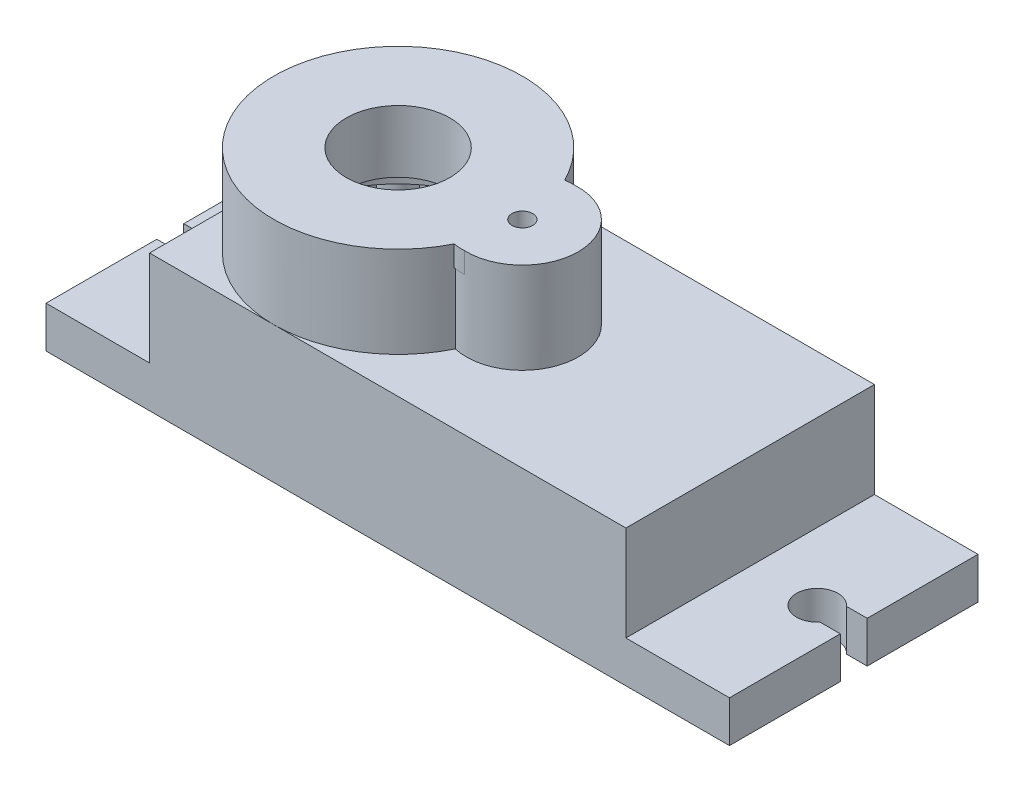
SolidWorks part; units mm, degrees
ref_plane "Front Plane" through (0, 0, 0) normal (0, 0, 1) x (1, 0, 0)
ref_plane "Top Plane" through (0, 0, 0) normal (0, 1, 0) x (1, 0, 0)
ref_plane "Right Plane" through (0, 0, 0) normal (1, 0, 0) x (0, 0, -1)
sketch "Sketch1" plane through (0, 0, 0) normal (0, 1, 0) x (1, 0, 0)
  line L1 (-11.5, -6) -> (11.5, -6)
  line L2 (-11.5, -6) -> (-11.5, 6)
  line L3 (-11.5, 6) -> (11.5, 6)
  line L4 (11.5, -6) -> (11.5, 6)
  line L5 (-11.5, -6) -> (11.5, 6) construction
  line L6 (-11.5, 6) -> (11.5, -6) construction
  point P0 (0, 0)
  dimension "D1" = 12
  dimension "D2" = 23
extrude "Boss-Extrude1" add sketch "Sketch1" along normal blind 6.6
sketch "Sketch2" plane through (11.5, 0, 0) normal (1, 0, 0) x (0, 0, -1)
  line L0 (-6, 0) -> (6, 0)
  line L1 (-6, 0) -> (-6, 2)
  line L2 (6, 0) -> (6, 2)
  line L3 (-6, 2) -> (6, 2)
  dimension "D1" = 2
extrude "Boss-Extrude2" add sketch "Sketch2" along normal blind 5 and the other way blind 28
sketch "Sketch3" plane through (0, 2, 0) normal (0, 1, 0) x (1, 0, 0)
  line L0 (16.5, 6) -> (16.5, -6) construction
  line L1 (16.5, 0.65) -> (15.5, 0.65)
  line L3 (16.5, -0.65) -> (15.5196, -0.65)
  line L5 (-16.5, 6) -> (-16.5, -6) construction
  line L7 (16.5, -0.65) -> (16.5, 0.65)
  line L9 (-16.5, -0.65) -> (-16.5, 0.65)
  line L10 (-16.5, -0.65) -> (-15.5196, -0.65)
  line L11 (-16.5, 0.65) -> (-15.5, 0.65)
  arc A0 (15.5, 0.65) -> (15.5196, -0.65) centre (14.75, -0.0114) ccw
  arc A1 (-15.5, 0.65) -> (-15.5196, -0.65) centre (-14.75, -0.0114) cw
  point P0 (16.5, 0)
  point P1 (-16.5, 0)
  point P2 (16.5, 0)
  dimension "D1" = 1
  dimension "D8" = 1
  dimension "D2" = 1
  dimension "D3" = 1.3
  dimension "D4" = 1.75
  dimension "D5" = 1.3
  dimension "D6" = 1
  dimension "D7" = 1.75
extrude "Cut-Extrude1" cut sketch "Sketch3" against normal blind 5
shell "Shell3" thickness 1 removed face at (0, 0, 0.0044)
sketch "Sketch5" plane through (0, 1, 0) normal (0, -1, 0) x (1, 0, 0)
  line L0 (10.5, -5) -> (11.5, -5)
  line L1 (10.5, -5) -> (15.5, -5) construction
  line L2 (11.5, -5) -> (11.5, 5)
  line L3 (-15.5, 5) -> (15.5, 5) construction
  line L4 (10.5, 5) -> (10.5, -5)
  line L5 (11.5, 5) -> (10.5, 5)
  line L6 (-10.5, 5) -> (-11.5, 5)
  line L7 (-15.5, 5) -> (-10.5, 5) construction
  line L8 (-11.5, 5) -> (-11.5, -5)
  line L9 (-15.5, -5) -> (-10.5, -5) construction
  line L10 (-11.5, -5) -> (-10.5, -5)
  line L11 (-10.5, -5) -> (-10.5, 5)
  dimension "D1" = 1
  dimension "D2" = 1
extrude "Boss-Extrude4" add sketch "Sketch5" along normal blind 1 contours L2 L5 L4 L0
extrude "Boss-Extrude5" add sketch "Sketch5<3>" along normal blind 1
sketch "Sketch5<3>" plane through (0, 1, 0) normal (0, -1, 0) x (1, 0, 0) same geometry as "Sketch5"
sketch "Sketch7" plane through (0, 6.6, 0) normal (0, 1, 0) x (1, 0, 0)
  line L0 (-11.5, 6) -> (-11.5, -6) construction
  line L1 (-16.5, -6) -> (16.5, -6) construction
  line L2 (-11.5, -6) -> (11.5, -6) construction
  arc A1 (-0.1075, 2.6308) -> (-0.1075, -2.6308) centre (-5.5, 0) ccw
  arc A2 (-0.1075, -2.6308) -> (-0.1075, 2.6308) centre (0.5, 0) ccw
  arc A3 (-0.3825, -2.0152) -> (-0.3825, 2.0152) centre (0.5, 0) ccw
  arc A4 (-0.3825, 2.0152) -> (-0.3825, -2.0152) centre (-5.5, 0) ccw
  dimension "D1" = 0.5
  dimension "D3" = 6
  dimension "D4" = 2.7
  dimension "D2" = 6
extrude "Boss-Extrude6" add sketch "Sketch7" along normal blind 4.4
sketch "Sketch19" plane through (0, 6.6, 0) normal (0, 1, 0) x (1, 0, 0)
  arc A0 (-0.4095, 2.0825) -> (-0.4095, -2.0825) centre (-5.5, 0) ccw
  arc A1 (-0.4095, -2.0825) -> (-0.4095, 2.0825) centre (0.3, 0) ccw
  dimension "D1" = 5.5
  dimension "D2" = 2.2
extrude "Cut-Extrude2" cut sketch "Sketch19" against normal through all
sketch "Sketch20" plane through (0, 11, 0) normal (0, 1, 0) x (1, 0, 0)
  arc A0 (-0.125, 2.6663) -> (-0.125, -2.6663) centre (-5.5, 0) ccw
  arc A1 (-0.125, -2.6663) -> (-0.125, 2.6663) centre (0.3, 0) ccw
  dimension "D1" = 6
  dimension "D2" = 2.7
extrude "Boss-Extrude7" add sketch "Sketch20" against normal blind 1
sketch "Sketch21" plane through (0, 11, 0) normal (0, 1, 0) x (1, 0, 0)
  circle A0 centre (-5.5, 0) radius 2.5
  circle A1 centre (0.5, 0) radius 0.5
  dimension "D1" = 5
  dimension "D2" = 1
extrude "Cut-Extrude3" cut sketch "Sketch21" against normal through all
sketch "Sketch22" plane through (0, 5.6, 0) normal (0, -1, 0) x (1, 0, 0)
  line L0 (-10.5, 5) -> (-7.7913, 5) construction
  line L1 (-10.5, 2.2913) -> (-10.5, 5) construction
  line L2 (0, 0) -> (-17.3923, 0) construction
  line L3 (0, 5) -> (0, -5) construction
  line L4 (10.5, -5) -> (-3.2087, -5) construction
  circle A0 centre (0.5, 0) radius 5.5
  circle A1 centre (-10.2, 4.7) radius 0.3
  circle A2 centre (-10.2, 4.7) radius 0.8
  circle A3 centre (-10.2, -4.7) radius 0.8
  circle A4 centre (10.2, -4.7) radius 0.8
  circle A5 centre (10.2, 4.7) radius 0.8
  dimension "D1" = 0.6
  dimension "D2" = 1.6
  dimension "D3" = 11
extrude "Cut-Extrude4" cut sketch "Sketch22" along normal through all contours A2 | A5 | A0 | A4 | A3
sketch "Sketch23" plane through (0, 5.6, 0) normal (0, -1, 0) x (1, 0, 0)
  line L0 (-11.5, 0) -> (11.5, 0)
  line L1 (-11.5, 5) -> (-11.5, -5) construction
  line L2 (11.5, -5) -> (11.5, 5) construction
  line L3 (0, 0) -> (0, 7.9375)
  circle A0 centre (-10.2, 4.7) radius 0.3
  circle A1 centre (-10.2, 4.7) radius 0.8
  circle A2 centre (-10.2, -4.7) radius 0.3
  circle A3 centre (-10.2, -4.7) radius 0.8
  circle A4 centre (10.2, -4.7) radius 0.8
  circle A5 centre (10.2, -4.7) radius 0.3
  circle A6 centre (10.2, 4.7) radius 0.3
  circle A7 centre (10.2, 4.7) radius 0.8
extrude "Boss-Extrude9" add sketch "Sketch23" along normal blind 2.5 contours A4 | A5 | A7 | A6 | A3 | A2 | A1 | A0
sketch "Sketch25" plane through (0, 10, 0) normal (0, -1, 0) x (1, 0, 0)
  circle A0 centre (-5.5, 0) radius 2.5
  circle A1 centre (-5.5, 0) radius 3.5
  dimension "D1" = 1
extrude "Boss-Extrude10" add sketch "Sketch25" along normal blind 2
